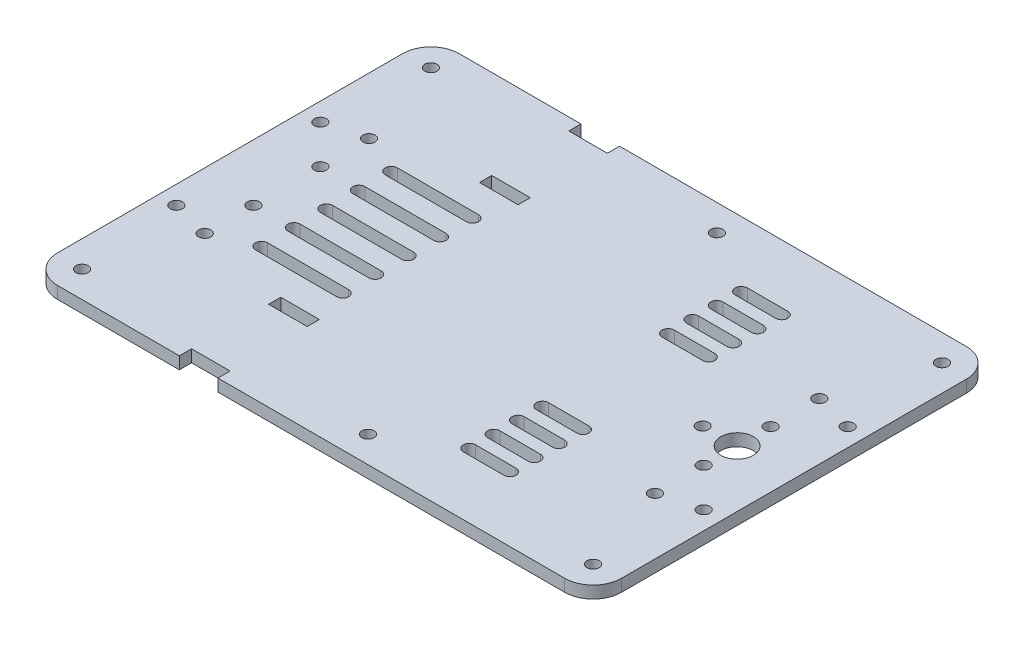
SolidWorks part; units mm, degrees
ref_plane "Front Plane" through (0, 0, 0) normal (0, 0, 1) x (1, 0, 0)
ref_plane "Top Plane" through (0, 0, 0) normal (0, 1, 0) x (1, 0, 0)
ref_plane "Right Plane" through (0, 0, 0) normal (1, 0, 0) x (0, 0, -1)
sketch "Sketch1" plane through (0, 0, 0) normal (0, 1, 0) x (1, 0, 0)
  line L0 (-32.5, 46.5) -> (-23, 46.5)
  line L1 (62.5, -49.5) -> (-62.5, -49.5)
  line L2 (69.5, -42.5) -> (69.5, 42.5)
  line L3 (62.5, 49.5) -> (-62.5, 49.5)
  line L4 (-69.5, -42.5) -> (-69.5, 42.5)
  line L5 (0, 49.5) -> (0, -49.5) construction
  line L6 (69.5, 0) -> (-69.5, 0) construction
  line L7 (-32.5, -49.5) -> (-23, -49.5)
  line L8 (-32.5, -49.5) -> (-32.5, -46.5)
  line L9 (-32.5, -46.5) -> (-23, -46.5)
  line L10 (-23, -49.5) -> (-23, -46.5)
  line L11 (-23, 49.5) -> (-23, 46.5)
  line L12 (-32.5, 49.5) -> (-23, 49.5)
  line L13 (-32.5, 49.5) -> (-32.5, 46.5)
  line L14 (-32.5, 24.5) -> (-23, 24.5)
  line L15 (-32.5, -27.5) -> (-23, -27.5)
  line L16 (-32.5, -27.5) -> (-32.5, -24.5)
  line L17 (-32.5, -24.5) -> (-23, -24.5)
  line L18 (-23, -27.5) -> (-23, -24.5)
  line L19 (-23, 27.5) -> (-23, 24.5)
  line L20 (-32.5, 27.5) -> (-23, 27.5)
  line L21 (-32.5, 27.5) -> (-32.5, 24.5)
  line L22 (-63, 43) -> (63, 43) construction
  line L23 (-63, -43) -> (63, -43) construction
  line L24 (33, 15.5) -> (23, 15.5) construction
  line L25 (33, 14) -> (23, 14)
  line L26 (33, 17) -> (23, 17)
  line L27 (33, -15.5) -> (23, -15.5) construction
  line L28 (33, -14) -> (23, -14)
  line L29 (33, -17) -> (23, -17)
  line L30 (-45.75, 16) -> (-25.75, 16) construction
  line L31 (-45.75, 17.5) -> (-25.75, 17.5)
  line L32 (-45.75, 14.5) -> (-25.75, 14.5)
  line L33 (-24.25, 27.75) -> (-24.25, 20.7276) construction
  line L34 (-45.75, 6.5) -> (-25.75, 6.5)
  line L35 (-45.75, 9.5) -> (-25.75, 9.5)
  line L36 (-45.75, 8) -> (-25.75, 8) construction
  line L37 (-45.75, -1.5) -> (-25.75, -1.5)
  line L38 (-45.75, 1.5) -> (-25.75, 1.5)
  line L39 (-45.75, 0) -> (-25.75, 0) construction
  line L40 (-45.75, -9.5) -> (-25.75, -9.5)
  line L41 (-45.75, -6.5) -> (-25.75, -6.5)
  line L42 (-45.75, -8) -> (-25.75, -8) construction
  line L43 (-45.75, -17.5) -> (-25.75, -17.5)
  line L44 (-45.75, -14.5) -> (-25.75, -14.5)
  line L45 (-45.75, -16) -> (-25.75, -16) construction
  line L46 (-63.5, 13.5) -> (-63.5, -10.25) construction
  line L47 (33, 23) -> (23, 23)
  line L48 (33, 20) -> (23, 20)
  line L49 (33, 21.5) -> (23, 21.5) construction
  line L50 (33, 29) -> (23, 29)
  line L51 (33, 26) -> (23, 26)
  line L52 (33, 27.5) -> (23, 27.5) construction
  line L53 (33, 35) -> (23, 35)
  line L54 (33, 32) -> (23, 32)
  line L55 (33, 33.5) -> (23, 33.5) construction
  line L56 (33, -33.5) -> (23, -33.5) construction
  line L57 (33, -32) -> (23, -32)
  line L58 (33, -35) -> (23, -35)
  line L59 (33, -27.5) -> (23, -27.5) construction
  line L60 (33, -26) -> (23, -26)
  line L61 (33, -29) -> (23, -29)
  line L62 (33, -21.5) -> (23, -21.5) construction
  line L63 (33, -20) -> (23, -20)
  line L64 (33, -23) -> (23, -23)
  arc A0 (69.5, 42.5) -> (62.5, 49.5) centre (62.5, 42.5) ccw
  arc A1 (62.5, -49.5) -> (69.5, -42.5) centre (62.5, -42.5) ccw
  arc A2 (-62.5, -49.5) -> (-69.5, -42.5) centre (-62.5, -42.5) cw
  arc A3 (-62.5, 49.5) -> (-69.5, 42.5) centre (-62.5, 42.5) ccw
  circle A4 centre (-63, 43) radius 1.5
  circle A5 centre (63, 43) radius 1.5
  circle A6 centre (63, -43) radius 1.5
  circle A7 centre (-63, -43) radius 1.5
  circle A8 centre (7.5, -43) radius 1.5
  circle A9 centre (7.5, 43) radius 1.5
  circle A10 centre (55.5, 8.25) radius 1.5
  circle A11 centre (55.5, -8.25) radius 1.5
  circle A12 centre (47, 0) radius 1.5
  arc A14 (33, 14) -> (33, 17) centre (33, 15.5) ccw
  arc A15 (23, 17) -> (23, 14) centre (23, 15.5) ccw
  arc A16 (33, -14) -> (33, -17) centre (33, -15.5) cw
  arc A17 (23, -17) -> (23, -14) centre (23, -15.5) cw
  circle A18 centre (55.5, -20.25) radius 1.5
  circle A20 centre (55.5, 20.25) radius 1.5
  arc A21 (-45.75, 17.5) -> (-45.75, 14.5) centre (-45.75, 16) ccw
  arc A22 (-25.75, 14.5) -> (-25.75, 17.5) centre (-25.75, 16) ccw
  arc A23 (-45.75, 9.5) -> (-45.75, 6.5) centre (-45.75, 8) ccw
  arc A24 (-25.75, 6.5) -> (-25.75, 9.5) centre (-25.75, 8) ccw
  arc A25 (-45.75, 1.5) -> (-45.75, -1.5) centre (-45.75, 0) ccw
  arc A26 (-25.75, -1.5) -> (-25.75, 1.5) centre (-25.75, 0) ccw
  arc A27 (-45.75, -6.5) -> (-45.75, -9.5) centre (-45.75, -8) ccw
  arc A28 (-25.75, -9.5) -> (-25.75, -6.5) centre (-25.75, -8) ccw
  arc A29 (-45.75, -14.5) -> (-45.75, -17.5) centre (-45.75, -16) ccw
  arc A30 (-25.75, -17.5) -> (-25.75, -14.5) centre (-25.75, -16) ccw
  circle A34 centre (-55.5, 20.25) radius 1.5
  circle A35 centre (-55.5, 8.25) radius 1.5
  circle A36 centre (-55.5, -8.25) radius 1.5
  circle A37 centre (-55.5, -20.25) radius 1.5
  circle A38 centre (-65, 17.75) radius 1.5
  circle A40 centre (-65, -17.75) radius 1.5
  circle A41 centre (65, 17.75) radius 1.5
  circle A42 centre (65, -17.75) radius 1.5
  circle A43 centre (55.5, 0) radius 4
  arc A44 (33, 20) -> (33, 23) centre (33, 21.5) ccw
  arc A45 (23, 23) -> (23, 20) centre (23, 21.5) ccw
  arc A46 (33, 26) -> (33, 29) centre (33, 27.5) ccw
  arc A47 (23, 29) -> (23, 26) centre (23, 27.5) ccw
  arc A48 (33, 32) -> (33, 35) centre (33, 33.5) ccw
  arc A49 (23, 35) -> (23, 32) centre (23, 33.5) ccw
  arc A50 (33, -32) -> (33, -35) centre (33, -33.5) cw
  arc A51 (23, -35) -> (23, -32) centre (23, -33.5) cw
  arc A52 (33, -26) -> (33, -29) centre (33, -27.5) cw
  arc A53 (23, -29) -> (23, -26) centre (23, -27.5) cw
  arc A54 (33, -20) -> (33, -23) centre (33, -21.5) cw
  arc A55 (23, -23) -> (23, -20) centre (23, -21.5) cw
  point P0 (0, 0)
  point P8 (69.5, -49.5)
  point P11 (-69.5, -49.5)
  point P15 (-69.5, 49.5)
  point P52 (28, 15.5)
  point P59 (28, -15.5)
  point P66 (-35.75, 16)
  point P79 (-35.75, 8)
  point P86 (-35.75, 0)
  point P93 (-35.75, -8)
  point P105 (-35.75, -16)
  point P133 (28, 21.5)
  point P140 (28, 27.5)
  point P147 (28, 33.5)
  point P154 (28, -33.5)
  point P161 (28, -27.5)
  point P168 (28, -21.5)
  dimension "D3" = 7
  dimension "D13" = 3
  dimension "D16" = 3
  dimension "D21" = 12
  dimension "D23" = 1.5
  dimension "D27" = 6
  dimension "D28" = 3
  dimension "D30" = 8
  dimension "D31" = 4
  dimension "D1" = 139
  dimension "D2" = 99
  dimension "D4" = 37
  dimension "D5" = 9.5
  dimension "D6" = 3
  dimension "D7" = 19
  dimension "D8" = 3
  dimension "D9" = 6.5
  dimension "D10" = 6.5
  dimension "D11" = 6.5
  dimension "D12" = 30.5
  dimension "D14" = 16.5
  dimension "D15" = 8.5
  dimension "D17" = 14
  dimension "D18" = 14
  dimension "D19" = 15.5
  dimension "D20" = 10
  dimension "D22" = 7
  dimension "D24" = 20
  dimension "D25" = 1.25
  dimension "D29" = 35.5
  dimension "D26" = 5
extrude "Boss-Extrude1" add sketch "Sketch1" along normal blind 3 contours L3 A3 L4 A2 L1 L8 L9 L10 A1 L2 A0 L11 L0 L13 L18 L15 L16 L17 L21 L20 L19 L14 region at (0.2831, 0, 0)
